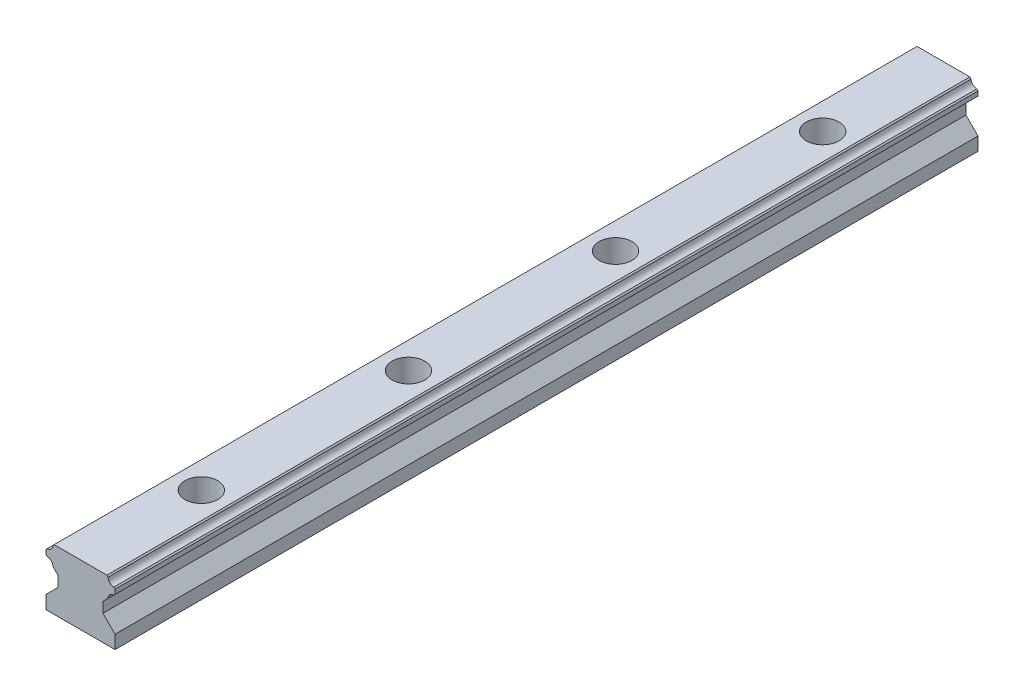
SolidWorks part; units mm, degrees
material "Plain Carbon Steel"
ref_plane "Front Plane" through (0, 0, 0) normal (0, 0, 1) x (1, 0, 0)
ref_plane "Top Plane" through (0, 0, 0) normal (0, 1, 0) x (1, 0, 0)
ref_plane "Right Plane" through (0, 0, 0) normal (1, 0, 0) x (0, 0, -1)
sketch "Sketch1" plane through (0, 0, 0) normal (0, 0, 1) x (1, 0, 0)
  line L0 (0, 13.3681) -> (0, -3.2505) construction
  line L1 (-6.5, -4.15) -> (-6.5, -7.15)
  line L3 (-6.5, -7.15) -> (-10, -10.65)
  line L4 (-10, -10.65) -> (-10, -14.5)
  line L5 (-8.0036, 2.6464) -> (-9.6464, 2.6464) construction
  line L6 (-10, -14.5) -> (0, -14.5)
  line L7 (-6.5, -4.15) -> (-8.0036, -2.6464)
  line L8 (-10, -0.65) -> (-10, 0.65)
  line L9 (-10, 0.65) -> (-9.6464, 1.0036)
  line L10 (-7.65, 3) -> (0, 3)
  line L11 (-10, -0.65) -> (-10, -10.65) construction
  line L12 (-10, 0) -> (0, 0) construction
  line L13 (-8.0036, 2.6464) -> (-7.65, 3)
  line L14 (-9.6464, -1.0036) -> (-10, -0.65)
  line L15 (0, 3) -> (0, -14.5)
  line L16 (-9.6464, 2.6464) -> (-9.6464, 1.0036) construction
  arc A0 (-9.6464, 1.0036) -> (-8.0036, 2.6464) centre (-9.6464, 2.6464) ccw
  arc A1 (-9.6464, -1.0036) -> (-8.0036, -2.6464) centre (-9.6464, -2.6464) cw
  dimension "D5" = 0.5
  dimension "D1" = 14.5
  dimension "D2" = 3
  dimension "D3" = 7.65
  dimension "D4" = 10
  dimension "D6" = 1.3
  dimension "D7" = 17.5
  dimension "D8" = 6.5
  dimension "D9" = 45
extrude "Boss-Extrude1" add sketch "Sketch1" along normal blind 125
mirror "Mirror1" about plane through (0, 3, 125) normal (-1, 0, 0) of "Boss-Extrude1"
sketch "Sketch2" plane through (0, 3, 0) normal (0, 1, 0) x (1, 0, 0)
  line L0 (0, 130.187) -> (0, 31.9327) construction
  line L1 (7.65, 0) -> (-7.65, 0) construction
  circle A0 centre (0, -30) radius 3
  dimension "D1" = 6
  dimension "D2" = 30
extrude "Cut-Extrude1" cut sketch "Sketch2" against normal through all
sketch "Sketch3" plane through (0, 3, 0) normal (0, 1, 0) x (1, 0, 0)
  circle A0 centre (0, -30) radius 4.75
  dimension "D1" = 9.5
extrude "Cut-Extrude2" cut sketch "Sketch3" against normal blind 8.5
pattern_linear "LPattern1" count 100 spacing 60 along (0, 0, 1) of "Cut-Extrude1", "Cut-Extrude2"
mirror "Mirror2" about plane through (-9.6464, -2.6464, 0) normal (0, 0, -1) of bodies 106
equation "\"length\"= 250mm"
equation "\"D1@Boss-Extrude1\"  = \"length\" /2"
equation "\"M5_tap\"=4.2mm\t\t\t\t\t\t\t' Below you can do mesurements as follows: cm, mm, ft, in, m, "
equation "\"M5_clearence\"=5.5mm"
equation "\"M6_tap\"=5mm"
equation "\"M6_clearence\"=6.6mm"
equation "\"work_area_width\"=1100mm"
equation "\"work_area_depth\"=900mm"
